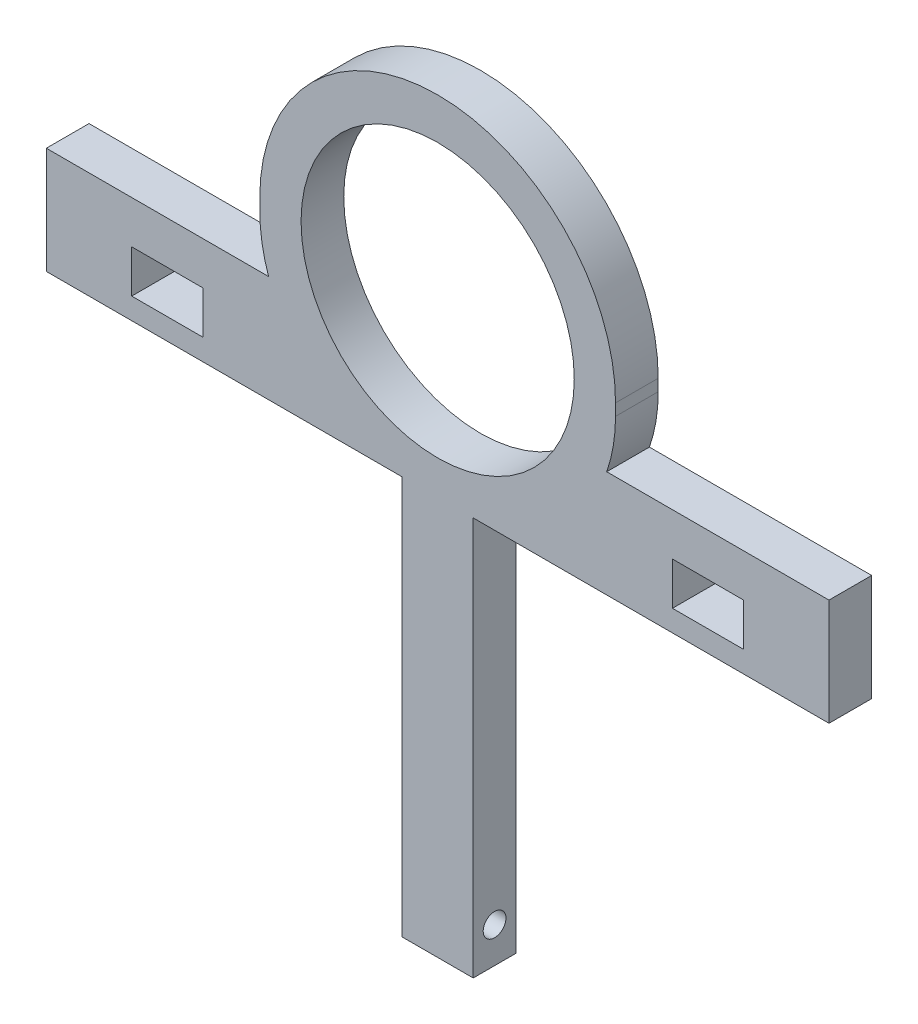
SolidWorks part; units mm, degrees
ref_plane "Front Plane" through (0, 0, 0) normal (0, 0, 1) x (1, 0, 0)
ref_plane "Top Plane" through (0, 0, 0) normal (0, 1, 0) x (1, 0, 0)
ref_plane "Right Plane" through (0, 0, 0) normal (1, 0, 0) x (0, 0, -1)
sketch "Sketch1" plane through (0, 0, 0) normal (0, 0, 1) x (1, 0, 0)
  circle A0 centre (0, 0) radius 31.75
  dimension "D2" = 63.5
extrude "Boss-Extrude1" add sketch "Sketch1" along normal blind 7.62
sketch "Sketch2" plane through (0, 0, 7.62) normal (0, 0, 1) x (1, 0, 0)
  line L1 (-31.75, 0) -> (31.75, 0)
  line L2 (-31.75, 0) -> (-31.75, -101.6)
  line L3 (-31.75, -101.6) -> (31.75, -101.6)
  line L4 (31.75, 0) -> (31.75, -101.6)
  circle A0 centre (0, 0) radius 31.75 construction
  dimension "D1" = 101.6
extrude "Boss-Extrude2" add sketch "Sketch2" along normal blind 7.62 from surface starting at face at (31.75, 0, 0)
sketch "Sketch4" plane through (0, 0, 7.62) normal (0, 0, 1) x (1, 0, 0)
  line L1 (-31.75, -101.6) -> (-6.35, -101.6)
  line L2 (-31.75, -101.6) -> (-31.75, -30.48)
  line L3 (-31.75, -30.48) -> (-6.35, -30.48)
  line L4 (-6.35, -101.6) -> (-6.35, -30.48)
  line L5 (31.75, -101.6) -> (6.35, -101.6)
  line L6 (31.75, -101.6) -> (31.75, -30.48)
  line L7 (31.75, -30.48) -> (6.35, -30.48)
  line L8 (6.35, -101.6) -> (6.35, -30.48)
  dimension "D1" = 25.4
  dimension "D2" = 71.12
extrude "Cut-Extrude2" cut sketch "Sketch4" against normal through all
fillet "Fillet1" radius 28.575 2 edges at (31.75, -30.48, 3.81) (-31.75, -30.48, 3.81)
sketch "Sketch6" plane through (-6.35, 0, 0) normal (-1, 0, 0) x (0, 0, 1)
  line L12 (7.62, -30.48) -> (0, -30.48)
  line L17 (7.62, -30.48) -> (7.62, -11.43)
  line L18 (7.62, -11.43) -> (0, -11.43)
  line L19 (0, -30.48) -> (0, -11.43)
  dimension "D1" = 19.05
extrude "Boss-Extrude3" add sketch "Sketch6" along normal blind 63.5
mirror "Mirror1" about plane through (0, 0, 0) normal (1, 0, 0) of "Boss-Extrude3"
sketch "Sketch5" plane through (-6.35, 0, 0) normal (-1, 0, 0) x (0, 0, 1)
  line L0 (3.81, -101.6) -> (3.81, -95.25) construction
  line L1 (0, -101.6) -> (7.62, -101.6) construction
  circle A0 centre (3.81, -95.25) radius 2.032
  dimension "D2" = 4.064
  dimension "D1" = 6.35
extrude "Cut-Extrude3" cut sketch "Sketch5" against normal through all
sketch "Sketch3" plane through (0, 0, 7.62) normal (0, 0, 1) x (1, 0, 0)
  circle A0 centre (0, 0) radius 24.384
  dimension "D1" = 48.768
extrude "Cut-Extrude1" cut sketch "Sketch3" against normal blind 7.62
sketch "Sketch7" plane through (0, 0, 7.62) normal (0, 0, 1) x (1, 0, 0)
  line L1 (-69.85, -30.48) -> (-54.61, -30.48) construction
  line L2 (-69.85, -30.48) -> (-69.85, -26.67) construction
  line L3 (-69.85, -26.67) -> (-54.61, -26.67) construction
  line L4 (-54.61, -30.48) -> (-54.61, -26.67) construction
  line L5 (-54.61, -26.67) -> (-41.91, -26.67)
  line L6 (-54.61, -26.67) -> (-54.61, -19.05)
  line L7 (-54.61, -19.05) -> (-41.91, -19.05)
  line L8 (-41.91, -26.67) -> (-41.91, -19.05)
  dimension "D1" = 15.24
  dimension "D2" = 3.81
  dimension "D3" = 7.62
  dimension "D4" = 12.7
extrude "Cut-Extrude4" cut sketch "Sketch7" against normal through all
mirror "Mirror2" about plane through (0, 0, 0) normal (1, 0, 0) of "Cut-Extrude4"
equation "\"Foamcore\" = .1in"
equation "\"MDF\" = .3in"
equation "\"Gmaterial\"= \"MDF\""
equation "\"PVC-ID\" = \"1.590in\""
equation "\"PVC-OD\" = \"1.900in\""
equation "\"PVC-Sleeve-Width\" = \".51in\""
equation "\"D1@Boss-Extrude1\"=\"Gmaterial\""
equation "\"D1@Boss-Extrude2\"=\"Gmaterial\""
equation "\"D3@Sketch7\"=\"Gmaterial\""
